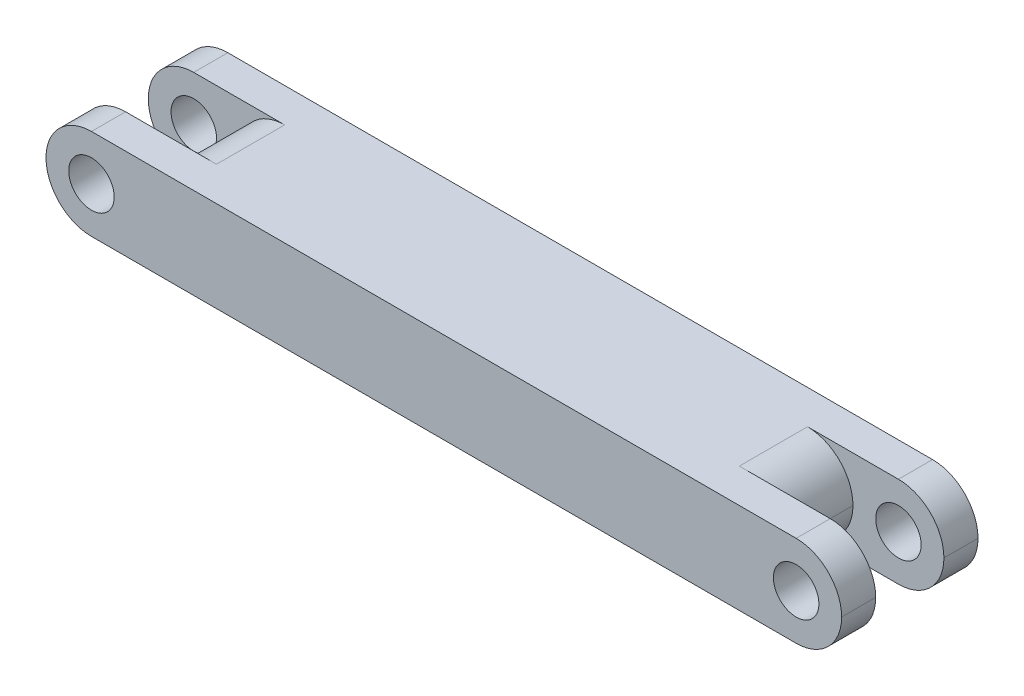
SolidWorks part; units mm, degrees
ref_plane "Ön Düzlem" through (0, 0, 0) normal (0, 0, 1) x (1, 0, 0)
ref_plane "Üst Düzlem" through (0, 0, 0) normal (0, 1, 0) x (1, 0, 0)
ref_plane "Sağ Düzlem" through (0, 0, 0) normal (1, 0, 0) x (0, 0, -1)
sketch "Çizim1" plane through (0, 0, 0) normal (0, 1, 0) x (1, 0, 0)
  line L0 (-246.467, 0) -> (246.467, 0) construction
  line L1 (-135, -15) -> (-135, 15)
  line L2 (-135, 15) -> (-175, 15)
  line L3 (-175, 15) -> (-175, 30)
  line L4 (-175, 30) -> (175, 30)
  line L5 (175, 30) -> (175, 15)
  line L6 (175, 15) -> (135, 15)
  line L7 (135, 15) -> (135, -15)
  line L8 (175, -15) -> (135, -15)
  line L9 (175, -30) -> (175, -15)
  line L10 (-175, -30) -> (175, -30)
  line L11 (-175, -15) -> (-175, -30)
  line L12 (-135, -15) -> (-175, -15)
  point P11 (0, 30)
  point P14 (135, 0)
  point P19 (-135, 0)
  dimension "D1" = 15
  dimension "D2" = 40
  dimension "D3" = 350
  dimension "D4" = 15
extrude "Yükseklik-Ekstrüzyon1" add sketch "Çizim1" against normal blind 40
sketch "Çizim2" plane through (0, 0, 30) normal (0, 0, 1) x (1, 0, 0)
  line L0 (-175, -40) -> (-175, 0) construction
  line L1 (-175, 0) -> (175, 0) construction
  line L2 (0, 48.8192) -> (0, -87.3272) construction
  circle A0 centre (-155, -20) radius 10
  circle A1 centre (155, -20) radius 10
  dimension "D1" = 20
  dimension "D2" = 20
  dimension "D3" = 20
extrude "Kes-Ekstrüzyon1" cut sketch "Çizim2" against normal up to surface (60 mm away) up to face at (0, -20, -30)
fillet "Radyus1" radius 20 12 edges at (135, -40, 0) (135, 0, 0) (-135, -40, 0) (-135, 0, 0) (-175, -40, -22.5) (-175, 0, -22.5) (-175, 0, 22.5) (-175, -40, 22.5) (175, 0, -22.5) (175, -40, -22.5) (175, -40, 22.5) (175, 0, 22.5)
ref_plane "Plane1" through (0, 0, 0) normal (0, 0, 1) x (1, 0, 0)
sketch "Sketch5" plane through (0, 0, 0) normal (0, 0, 1) x (1, 0, 0)
  point P0 (-155, -20)
  point P1 (155, -20)
